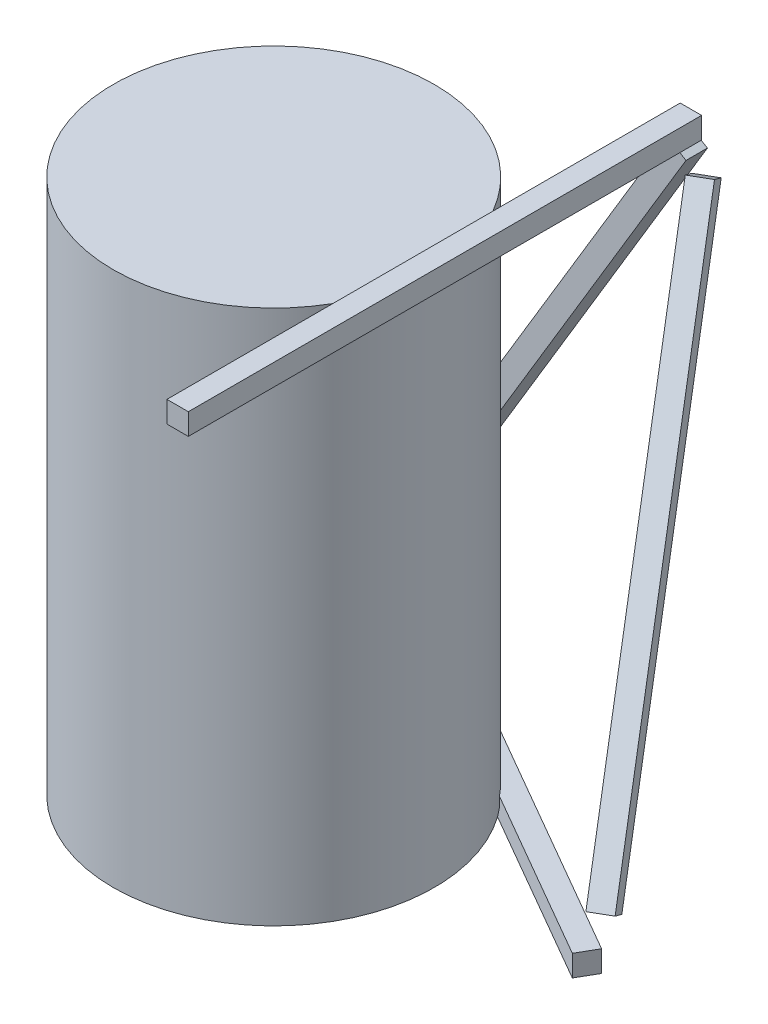
SolidWorks part; units mm, degrees
note: '?' marks a value the reader was unsure of.
ref_plane "Alzado" through (0, 0, 0) normal (0, 0, 1) x (1, 0, 0)
ref_plane "Planta" through (0, 0, 0) normal (0, 1, 0) x (1, 0, 0)
ref_plane "Vista lateral" through (0, 0, 0) normal (1, 0, 0) x (0, 0, -1)
sketch "Croquis1" plane through (0, 0, 0) normal (0, 1, 0) x (1, 0, 0)
  line L1 (300, 0) -> (-150, 259.8076)
  line L2 (-150, 259.8076) -> (-150, -259.8076)
  line L3 (-150, -259.8076) -> (300, 0)
  circle A0 centre (0, 0) radius 150 construction
  dimension "D1" = 300
surface "Superficie-Plano1" sketch "Croquis1"
sketch "Croquis4" plane through (0, 0, 0) normal (0, 1, 0) x (1, 0, 0)
  circle A0 centre (0, 0) radius 150
  dimension "D1" = 300
extrude "Saliente-Extruir1" add sketch "Croquis4" along normal blind 500
ref_plane "hith" through (0, 500, 0) normal (0, 1, 0) x (1, 0, 0)
ref_axis "Eje1" through (0, 0, 0) along (0, 1, 0)?
ref_plane "simetria" through (0, 250, 0) normal (0, 1, 0) x (1, 0, 0)
sketch "Croquis2" plane through (0, 500, 0) normal (0, 1, 0) x (1, 0, 0)
  line L1 (-300, 0) -> (150, -259.8076)
  line L2 (150, -259.8076) -> (150, 259.8076)
  line L3 (150, 259.8076) -> (-300, 0)
  circle A0 centre (0, 0) radius 150 construction
  dimension "D1" = 300
surface "Superficie-Plano2" sketch "Croquis2"
ref_axis "Eje2" through (150, 500, 259.8076) along (0.2572, -0.8575, -0.4456)?
ref_axis "Eje3" through (150, 500, -259.8076) along (0.2572, -0.8575, 0.4456)?
ref_axis "Eje4" through (150, 500, -259.8076) along (-0.5145, -0.8575, 0)?
ref_axis "Eje5" through (-150, 0, -259.8076) along (-0.2572, 0.8575, 0.4456)?
ref_axis "Eje6" through (-300, 500, 0) along (0.2572, -0.8575, 0.4456)?
ref_axis "Eje7" through (150, 500, 259.8076) along (-0.5145, -0.8575, 0)?
ref_point "Punto1"
ref_point "Punto2"
ref_plane "Plano1" through (150, 500, -259.8076) normal (-0.5145, -0.8575, 0) x (-0.8575, 0.5145, 0)
ref_plane "Plano2" through (-150, 0, -259.8076) normal (-0.5145, -0.8575, 0) x (-0.8575, 0.5145, 0)
ref_plane "Plano3" through (110.2941, 183.8235, 0) normal (-0.5145, -0.8575, 0) x (-0.8575, 0.5145, 0)
sketch "Croquis5" plane through (110.2941, 183.8235, 0) normal (-0.5145, -0.8575, 0) x (-0.8575, 0.5145, 0)
  line L0 (128.6239, -259.8076) -> (128.6239, 259.8076) construction
  line L1 (138.6239, 249.8076) -> (118.6239, 249.8076)
  line L2 (138.6239, 249.8076) -> (138.6239, 269.8076)
  line L3 (138.6239, 269.8076) -> (118.6239, 269.8076)
  line L4 (118.6239, 249.8076) -> (118.6239, 269.8076)
  line L5 (138.6239, 249.8076) -> (118.6239, 269.8076) construction
  line L6 (138.6239, 269.8076) -> (118.6239, 249.8076) construction
  point P0 (128.6239, 259.8076)
  dimension "D1" = 20
  dimension "D2" = 20
extrude "Saliente-Extruir2" add sketch "Croquis5" along normal mid plane 493.0952 separate body
ref_point "Punto3"
ref_point "Punto5"
ref_plane "Plano5" through (150, 500, 259.8076) normal (0, 0, -1) x (-1, 0, 0)
ref_plane "Plano6" through (150, 500, -259.8076) normal (0, 0, -1) x (-1, 0, 0)
ref_plane "Plano7" through (0, 0, 0) normal (0, 0, -1) x (-1, 0, 0)
sketch "Croquis6" plane through (0, 0, 0) normal (0, 0, -1) x (-1, 0, 0)
  line L1 (-140, 490) -> (-160, 490)
  line L2 (-140, 490) -> (-140, 510)
  line L3 (-140, 510) -> (-160, 510)
  line L4 (-160, 490) -> (-160, 510)
  line L5 (-140, 490) -> (-160, 510) construction
  line L6 (-140, 510) -> (-160, 490) construction
  point P0 (-150, 500)
  dimension "D1" = 20
extrude "Saliente-Extruir3" add sketch "Croquis6" along normal mid plane 479.6152 separate body
ref_plane "Plano8" through (150, 500, -259.8076) normal (0.2572, -0.8575, 0.4456) x (-0.9658, -0.2431, 0.0898)
ref_plane "Plano9" through (300, 0, 0) normal (0.2572, -0.8575, 0.4456) x (-0.9658, -0.2431, 0.0898)
ref_plane "Plano10" through (-55.1471, 183.8235, -95.5175) normal (0.2572, -0.8575, 0.4456) x (-0.9658, -0.2431, 0.0898)
sketch "Croquis7" plane through (-55.1471, 183.8235, -95.5175) normal (0.2572, -0.8575, 0.4456) x (-0.9658, -0.2431, 0.0898)
  line L0 (168.2135, -236.1108) -> (-289.7517, 9.3843) construction
  line L1 (-303.2898, 5.2953) -> (-285.6627, -4.1538)
  line L2 (-303.2898, 5.2953) -> (-293.8407, 22.9224)
  line L3 (-293.8407, 22.9224) -> (-276.2136, 13.4733)
  line L4 (-285.6627, -4.1538) -> (-276.2136, 13.4733)
  line L5 (-303.2898, 5.2953) -> (-276.2136, 13.4733) construction
  line L6 (-293.8407, 22.9224) -> (-285.6627, -4.1538) construction
  point P0 (-289.7517, 9.3843)
  dimension "D1" = 20
extrude "Saliente-Extruir4" add sketch "Croquis7" along normal mid plane 493.0952 separate body
ref_plane "Plano11" through (-150, 0, -259.8076) normal (-0.866, 0, -0.5) x (-0.5, 0, 0.866)
ref_plane "Plano12" through (300, 0, 0) normal (-0.866, 0, -0.5) x (-0.5, 0, 0.866)
ref_plane "Plano13" through (0, 0, 0) normal (-0.866, 0, -0.5) x (-0.5, 0, 0.866)
sketch "Croquis8" plane through (0, 0, 0) normal (-0.866, 0, -0.5) x (-0.5, 0, 0.866)
  line L1 (-140, -10) -> (-160, -10)
  line L2 (-140, -10) -> (-140, 10)
  line L3 (-140, 10) -> (-160, 10)
  line L4 (-160, -10) -> (-160, 10)
  line L5 (-140, -10) -> (-160, 10) construction
  line L6 (-140, 10) -> (-160, -10) construction
  point P0 (-150, 0)
  dimension "D1" = 20
extrude "Saliente-Extruir5" add sketch "Croquis8" along normal mid plane 479.6152 separate body
equation "\"printarea\" = 300"
equation "\"D1@Croquis1\"=\"printarea\""
equation "\"D1@Croquis2\"=\"printarea\""
equation "\"hitg\" = 500"
equation "\"D1@Saliente-Extruir1\"=\"hitg\""
equation "\"perfil\"= 20"
equation "\"clear\"= .4"
equation "\"joind\" = 45"
equation "\"dist\" = \"RD3@Anotaciones\""
equation "\"D1@Saliente-Extruir2\"=\"dist\"-2*\"joind\""
equation "\"joind2\"= 20"
equation "\"D1@Croquis6\"=\"perfil\""
equation "\"D1@Croquis5\"= \"perfil\""
equation "\"D2@Croquis5\"= \"perfil\""
equation "\"distt\"= \"RD2@Anotaciones\""
equation "\"D1@Saliente-Extruir3\"=\"distt\"-2*\"joind2\""
equation "\"D1@Croquis7\"=\"perfil\""
equation "\"D1@Saliente-Extruir4\"=\"dist\"-2*\"joind\""
equation "\"D1@Croquis8\"=\"perfil\""
equation "\"D1@Saliente-Extruir5\"=\"distt\"-2*\"joind2\""
equation "\"D1@Croquis4\"=\"printarea\""
